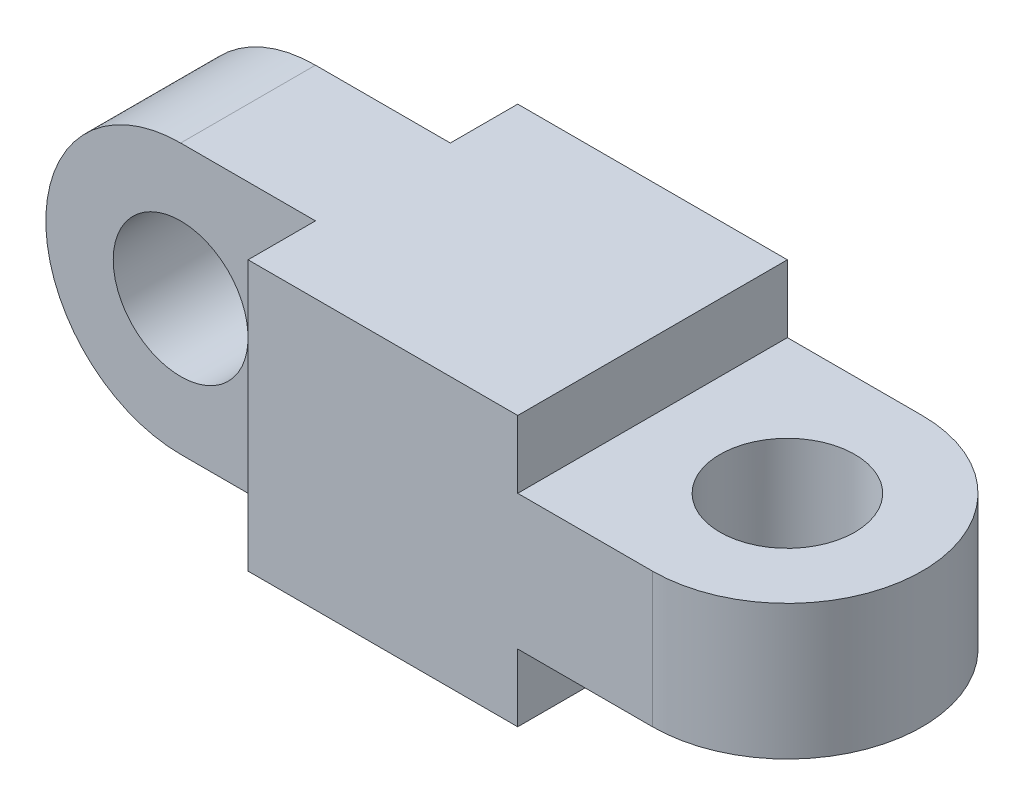
SolidWorks part; units mm, degrees
ref_plane "Plan de face" through (0, 0, 0) normal (0, 0, 1) x (1, 0, 0)
ref_plane "Plan de dessus" through (0, 0, 0) normal (0, 1, 0) x (1, 0, 0)
ref_plane "Plan de droite" through (0, 0, 0) normal (1, 0, 0) x (0, 0, -1)
sketch "Esquisse1" plane through (0, 0, 0) normal (0, 0, 1) x (1, 0, 0)
  line L0 (50, 5) -> (50, 15)
  line L1 (0, 0) -> (30, 0)
  line L2 (0, 0) -> (0, 20) construction
  line L3 (0, 20) -> (30, 20)
  line L4 (50, 0) -> (50, 5) construction
  line L5 (50, 15) -> (30, 15)
  line L6 (50, 15) -> (50, 5) construction
  line L7 (50, 5) -> (30, 5)
  line L8 (30, 15) -> (30, 5) construction
  line L9 (50, 15) -> (50, 20) construction
  line L10 (30, 15) -> (30, 20)
  line L11 (30, 5) -> (30, 0)
  line L12 (30, 20) -> (50, 20) construction
  line L13 (30, 0) -> (50, 0) construction
  arc A0 (0, 0) -> (0, 20) centre (0, 10) cw
  circle A1 centre (0, 10) radius 5
  point P11 (50, 10)
  point P12 (50, 10)
  dimension "D2" = 10
  dimension "D1" = 20
  dimension "D3" = 50
  dimension "D4" = 10
  dimension "D5" = 20
extrude "Boss.-Extru.1" add sketch "Esquisse1" along normal blind 20
sketch "Esquisse2" plane through (0, 0, 0) normal (0, 1, 0) x (1, 0, 0)
  line L0 (-10, -5) -> (-10, -15)
  line L1 (40, 0) -> (10, 0)
  line L2 (40, 0) -> (40, -20) construction
  line L3 (40, -20) -> (10, -20)
  line L4 (-10, 0) -> (-10, -5) construction
  line L5 (-10, -15) -> (10, -15)
  line L6 (-10, -15) -> (-10, -5) construction
  line L7 (-10, -5) -> (10, -5)
  line L8 (10, -15) -> (10, -5) construction
  line L9 (-10, -15) -> (-10, -20) construction
  line L10 (-10, 0) -> (-10, -20) construction
  line L11 (30, -20) -> (0, -20) construction
  line L12 (30, 0) -> (0, 0) construction
  line L13 (10, -5) -> (10, 0)
  line L14 (10, -15) -> (10, -20)
  line L15 (10, 0) -> (-10, 0) construction
  line L16 (10, -20) -> (-10, -20) construction
  arc A0 (40, 0) -> (40, -20) centre (40, -10) cw
  circle A1 centre (40, -10) radius 5
  point P11 (-10, -10)
  point P12 (-10, -10)
  dimension "D2" = 10
  dimension "D1" = 20
  dimension "D3" = 50
  dimension "D4" = 10
  dimension "D5" = 20
extrude "Boss.-Extru.2" add sketch "Esquisse2" along normal blind 20 separate body
combine bodies "Combiner1" operation type common bodies to combine 102 101
ref_axis "Axe1" through (40, 15, 10) along (0, -1, 0)
ref_axis "Axe2" through (0, 10, 15) along (0, 0, -1)
ref_plane "Plan1" through (0, 0, 10) normal (0, 0, 1) x (1, 0, 0)
ref_plane "Plan2" through (0, 10, 0) normal (0, 1, 0) x (1, 0, 0)
